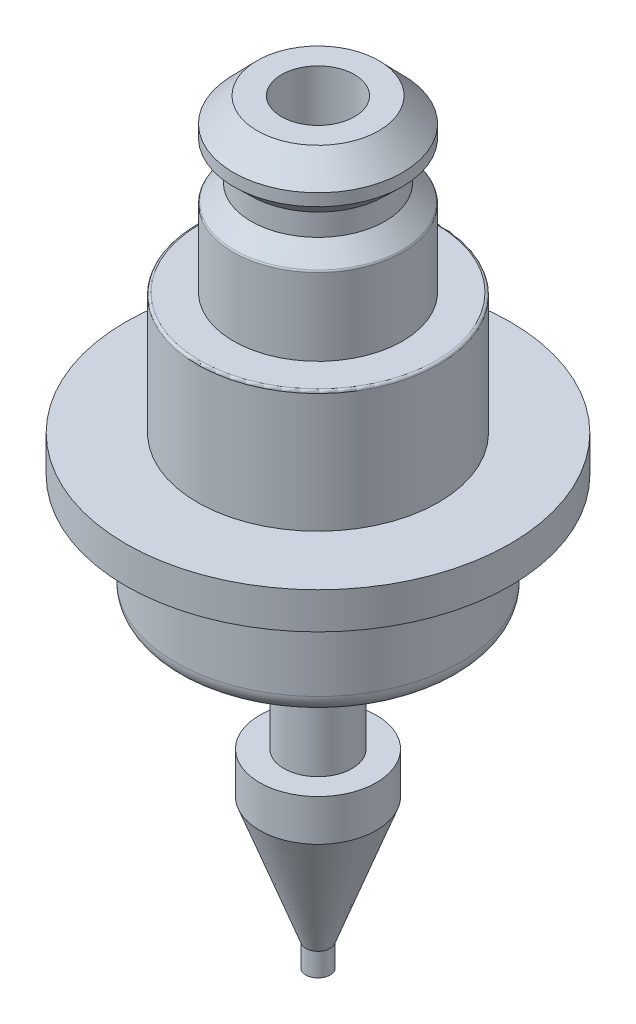
SolidWorks part; units mm, degrees
ref_plane "前视基准面" through (0, 0, 0) normal (0, 0, 1) x (1, 0, 0)
ref_plane "上视基准面" through (0, 0, 0) normal (0, 1, 0) x (1, 0, 0)
ref_plane "右视基准面" through (0, 0, 0) normal (1, 0, 0) x (0, 0, -1)
other "Configuration Table"
sketch "草图1" plane through (0, 0, 0) normal (0, 0, 1) x (1, 0, 0)
  line L0 (2.4, -9.75) -> (1.4, -9.75)
  line L1 (1.4, -9.75) -> (1.4, -4.5)
  line L2 (1.4, -4.5) -> (5.1, -4.5)
  line L3 (5.85, -3.75) -> (5.85, 0)
  line L4 (5.85, 0) -> (7.9, 0)
  line L5 (7.9, 0) -> (7.9, 1.5)
  line L6 (7.9, 1.5) -> (4.955, 1.5)
  line L7 (4.955, 1.5) -> (4.955, 6.4)
  line L8 (4.855, 6.5) -> (3.475, 6.5)
  line L9 (3.475, 6.5) -> (3.475, 9.6575)
  line L10 (3.4445, 9.7295) -> (2.75, 10.4)
  line L11 (2.75, 10.4) -> (2.75, 11.3)
  line L12 (2.75, 11.3) -> (3.475, 12)
  line L13 (3.475, 12) -> (3.475, 12.5)
  line L14 (3.475, 12.5) -> (2.5, 13.5)
  line L15 (2.5, 13.5) -> (1.5, 13.5)
  line L16 (1.5, 13.5) -> (1.5, 0)
  line L17 (1.5, 0) -> (0.15, 0)
  line L18 (0.15, 0) -> (0.15, -17.55)
  line L19 (0.15, -17.55) -> (2.4, -11.45)
  line L20 (2.4, -11.45) -> (2.4, -9.75)
  line L21 (0, 13.5) -> (0, -17.55) construction
  line L22 (3.475, 9.6575) -> (3.475, 9.7) construction
  line L23 (3.4445, 9.7295) -> (3.475, 9.7) construction
  arc A0 (5.1, -4.5) -> (5.85, -3.75) centre (5.1, -3.75) ccw
  arc A1 (4.955, 6.4) -> (4.855, 6.5) centre (4.855, 6.4) ccw
  arc A2 (3.475, 9.6575) -> (3.4445, 9.7295) centre (3.375, 9.6575) ccw
  point P29 (6.4275, 1.5)
  point P31 (3.475, 9.7)
  dimension "D14" = 0.1
  dimension "D16" = 0.1
  dimension "D20" = 0.75
  dimension "D1" = 7
  dimension "D2" = 31.05
  dimension "D3" = 1.5
  dimension "D4" = 4.5
  dimension "D5" = 13.05
  dimension "D6" = 5
  dimension "D7" = 1.5
  dimension "D8" = 0.15
  dimension "D9" = 1
  dimension "D10" = 0.5
  dimension "D11" = 0.7
  dimension "D12" = 0.9
  dimension "D13" = 0.7
  dimension "D15" = 3.2
  dimension "D17" = 1.7
  dimension "D18" = 6.1
  dimension "D19" = 5.25
  dimension "D21" = 2.4
  dimension "D22" = 1.4
  dimension "D23" = 5.85
  dimension "D24" = 7.9
  dimension "D25" = 4.955
  dimension "D26" = 3.475
  dimension "D27" = 2.75
  dimension "D28" = 3.475
  dimension "D29" = 1
  dimension "D30" = 6
revolve "旋转1" add sketch "草图1" angle 360 about L21 reverse direction yes
ref_plane "基准面1" through (0, -17.55, 0) normal (0, -1, 0) x (-1, 0, 0)
sketch "草图2" plane through (0, -17.55, 0) normal (0, -1, 0) x (-1, 0, 0)
  circle A0 centre (0, 0) radius 0.15 construction
  circle A1 centre (0, 0) radius 0.15
  circle A2 centre (0, 0) radius 0.5
  dimension "D1" = 0.3
  dimension "D2" = 1
extrude "凸台-拉伸1" add sketch "草图2" against normal blind 1
ref_axis "基准轴1" through (0, -7.7092, 0) along (0, -1, 0)
